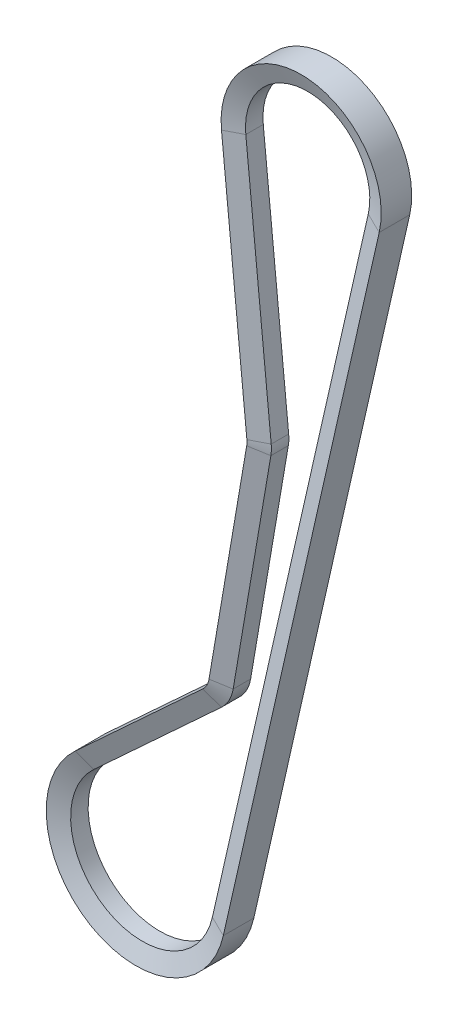
SolidWorks part; units mm, degrees
ref_plane "Front Plane" through (0, 0, 0) normal (0, 0, 1) x (1, 0, 0)
ref_plane "Top Plane" through (0, 0, 0) normal (0, 1, 0) x (1, 0, 0)
ref_plane "Right Plane" through (0, 0, 0) normal (1, 0, 0) x (0, 0, -1)
sketch "Sketch2" plane through (0, 0, 0) normal (0, 0, 1) x (1, 0, 0)
  line L0 (0, 0) -> (1, 0) construction
  line L1 (0, 0) -> (0, 1) construction
  line L12 (24.3802, -5.5325) -> (-24.3009, -220.0579)
  line L14 (-70.5858, -193.2753) -> (-30.7263, -156.5276)
  line L15 (-28.7709, -152.9265) -> (-17.0019, -83.923)
  line L16 (-16.9427, -82.2267) -> (-24.8772, -2.475)
  arc A4 (-24.3009, -220.0579) -> (-70.5858, -193.2753) centre (-51.6067, -213.8615) cw
  arc A7 (-24.8772, -2.475) -> (24.3802, -5.5325) centre (0, 0) cw
  arc A8 (-30.7263, -156.5276) -> (-28.7709, -152.9265) centre (-35.0305, -151.8589) ccw
  arc A9 (-17.0019, -83.923) -> (-16.9427, -82.2267) centre (-23.2615, -82.8553) ccw
ref_plane "Plane4" through (-24.8772, -2.475, 0) normal (-0.099, 0.9951, 0) x (0.9951, 0.099, 0)
sketch "Sketch3" plane through (-24.8772, -2.475, 0) normal (-0.099, 0.9951, 0) x (0.9951, 0.099, 0)
  line L0 (0, -4.7625) -> (0, 4.7625)
  line L1 (0, -4.7625) -> (5.588, -2.7286)
  line L2 (5.588, -2.7286) -> (5.588, 2.7286)
  line L3 (5.588, 2.7286) -> (0, 4.7625)
  line L4 (0, 0) -> (5.588, 0) construction
  dimension "D1" = 9.525
  dimension "D2" = 5.588
  dimension "D3" = 40
sweep "Sweep1" add profiles "Sketch3" path "Sketch2"
